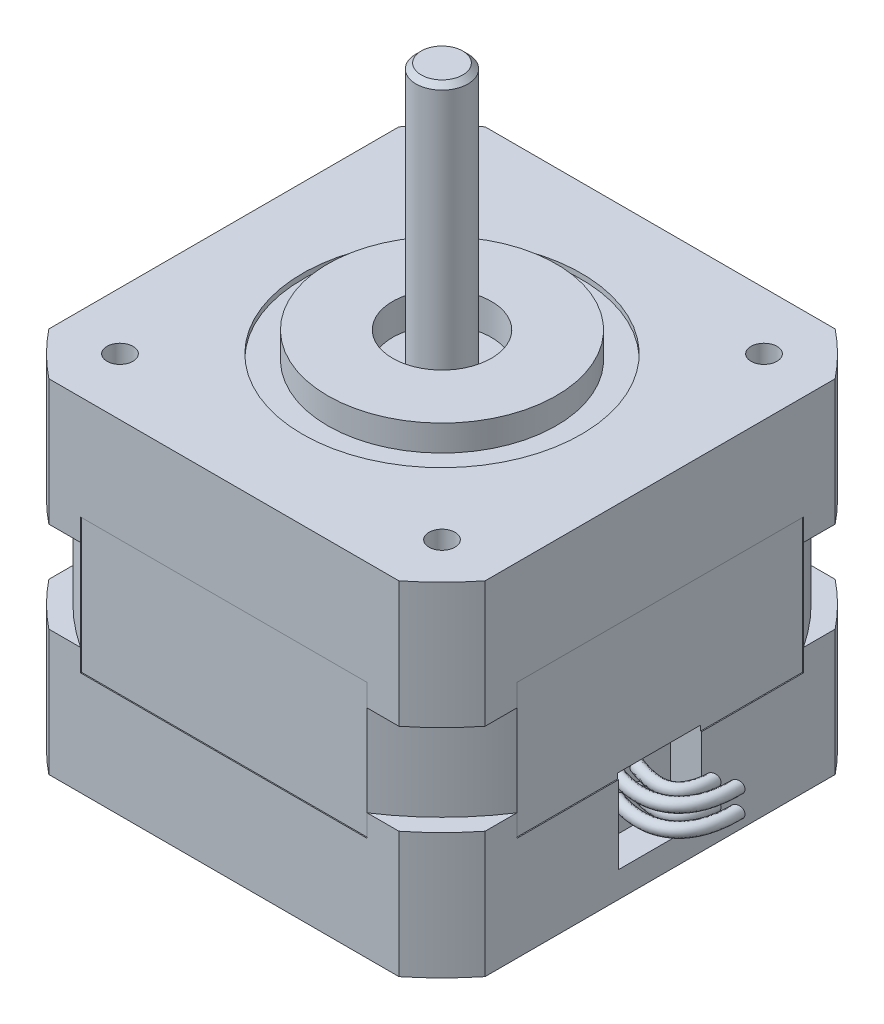
SolidWorks part; units mm, degrees
ref_plane "Front Plane" through (0, 0, 0) normal (0, 0, 1) x (1, 0, 0)
ref_plane "Top Plane" through (0, 0, 0) normal (0, 1, 0) x (1, 0, 0)
ref_plane "Right Plane" through (0, 0, 0) normal (1, 0, 0) x (0, 0, -1)
sketch "Sketch1" plane through (0, 0, 0) normal (0, 1, 0) x (1, 0, 0)
  line L0 (0, -21) -> (0, 21) construction
  line L1 (-21, 16.851) -> (-21, -16.851)
  line L2 (-16.851, -21) -> (16.851, -21)
  line L3 (21, -16.851) -> (21, 16.851)
  line L4 (16.851, 21) -> (-16.851, 21)
  line L5 (-21, 0) -> (21, 0) construction
  arc A0 (-21, 16.851) -> (-16.851, 21) centre (0, 0) cw
  arc A1 (16.851, 21) -> (21, 16.851) centre (0, 0) cw
  arc A2 (21, -16.851) -> (16.851, -21) centre (0, 0) cw
  arc A3 (-21, -16.851) -> (-16.851, -21) centre (0, 0) ccw
  dimension "D3" = 26.925
  dimension "D1" = 42
  dimension "D2" = 42
extrude "Boss-Extrude2" add sketch "Sketch1" along normal blind 33
sketch "Sketch3" plane through (0, 0, 0) normal (0, 0, 1) x (1, 0, 0)
  line L0 (0, -2.0131) -> (0, 34.8611) construction
  line L1 (-30.125, 20.875) -> (-25.125, 20.875)
  line L2 (-30.125, 20.875) -> (-30.125, 12.125)
  line L3 (-30.125, 12.125) -> (-25.125, 12.125)
  line L4 (-25.125, 20.875) -> (-25.125, 12.125)
  line L5 (21, 16.5) -> (-21, 16.5) construction
  line L6 (21, 33) -> (21, 0) construction
  line L7 (-21, 33) -> (-21, 0) construction
  point P13 (-25.125, 16.5)
  dimension "D1" = 8.75
  dimension "D2" = 25.125
  dimension "D3" = 5
revolve "Cut-Revolve1" cut sketch "Sketch3" angle 360 about L0
sketch "Sketch4" plane through (0, 33, 0) normal (0, 1, 0) x (1, 0, 0)
  circle A0 centre (0, 0) radius 13.425
  dimension "D1" = 26.85
extrude "Cut-Extrude1" cut sketch "Sketch4" against normal blind 0.5
sketch "Sketch5" plane through (0, 32.5, 0) normal (0, 1, 0) x (1, 0, 0)
  circle A0 centre (0, 0) radius 11
  dimension "D1" = 22
extrude "Boss-Extrude3" add sketch "Sketch5" along normal blind 2.5
sketch "Sketch6" plane through (0, 35, 0) normal (0, 1, 0) x (1, 0, 0)
  circle A0 centre (0, 0) radius 4.75
  dimension "D1" = 9.5
extrude "Cut-Extrude2" cut sketch "Sketch6" against normal blind 3
sketch "Sketch7" plane through (0, 32, 0) normal (0, 1, 0) x (1, 0, 0)
  circle A0 centre (0, 0) radius 2.5
  dimension "D1" = 5
extrude "Boss-Extrude4" add sketch "Sketch7" along normal blind 25.25
chamfer "Chamfer1" distance 0.5 angle 45 1 edges at (0, 57.25, 2.5)
sketch "Sketch8" plane through (0, 0, 0) normal (0, -1, 0) x (1, 0, 0)
  circle A0 centre (0, 0) radius 4.5
  dimension "D1" = 9
extrude "Cut-Extrude3" cut sketch "Sketch8" against normal blind 3
sketch "Sketch9" plane through (0, 33, 0) normal (0, 1, 0) x (1, 0, 0)
  line L0 (-15.5, 15.5) -> (15.5, 15.5) construction
  line L1 (15.5, 15.5) -> (15.5, -15.5) construction
  line L2 (15.5, -15.5) -> (-15.5, -15.5) construction
  line L3 (-15.5, -15.5) -> (-15.5, 15.5) construction
  point P2 (-15.5, 0)
  point P5 (0, 15.5)
  dimension "D1" = 31
  dimension "D2" = 31
hole_wizard "M3x0.5 Tapped Hole1" positions "Sketch11" profile "Sketch10" tap size "M3x0.5" standard "ANSI Metric"
sketch "Sketch11" plane through (0, 33, 0) normal (0, 1, 0) x (1, 0, 0)
  point P0 (-15.5, -15.5)
  point P3 (-15.5, 15.5)
  point P6 (15.5, 15.5)
  point P9 (15.5, -15.5)
sketch "Sketch10" plane through (-15.5, 33, 15.5) normal (1, 0, 0) x (0, 0, 1)
  line L0 (0, 0) -> (0, 5.2511)
  line L1 (0, 5.2511) -> (1.25, 4.5)
  line L2 (1.25, 4.5) -> (1.25, 0)
  line L5 (1.25, 0) -> (0, 0)
  line L10 (0, 5.2511) -> (-1.25, 4.5) construction
  line L11 (0, -6.35) -> (0, 107.95) construction
  dimension "Tap Drill Dia." = 2.5
  dimension "Tap Drill Depth" = 4.5
  dimension "Drill Angle" = 118
sketch "Sketch12" plane through (21, 0, 0) normal (1, 0, 0) x (0, 0, -1)
  line L0 (-16.851, 0) -> (16.851, 0) construction
  line L1 (-4, 10.5) -> (4, 10.5)
  line L2 (-4, 10.5) -> (-4, 2.5)
  line L3 (-4, 2.5) -> (4, 2.5)
  line L4 (4, 10.5) -> (4, 2.5)
  point P4 (0, 2.5)
  dimension "D1" = 8
  dimension "D2" = 8
  dimension "D3" = 2.5
extrude "Cut-Extrude4" cut sketch "Sketch12" against normal blind 3
sketch "Sketch13" plane through (18, 0, 0) normal (1, 0, 0) x (0, 0, -1)
  circle A0 centre (-1.1125, 7.415) radius 0.6
  circle A1 centre (0.707, 7.415) radius 0.6
  circle A2 centre (-1.1125, 5.3322) radius 0.6
  circle A3 centre (0.707, 5.3322) radius 0.6
  dimension "D1" = 1.2
sketch "Sketch14" plane through (0, 0, 0) normal (0, 1, 0) x (1, 0, 0)
  spline S0 degree 2 poles (17.6767, 0) (23.6461, -2.3668) (23.7984, 3.3576) knots 0 0 0 1 1 1
sweep "Sweep2" add profiles "Sketch13" path "Sketch14"
sketch "Sketch15" plane through (0, 0, -21) normal (0, 0, -1) x (-1, 0, 0)
  line L0 (-13.7937, 12.125) -> (-13.7937, 20.875) construction
  line L1 (-13.7937, 23) -> (13.7937, 23)
  line L2 (-13.7937, 23) -> (-13.7937, 10)
  line L3 (-13.7937, 10) -> (13.7937, 10)
  line L4 (13.7937, 23) -> (13.7937, 10)
  line L5 (13.7937, 20.875) -> (13.7937, 12.125) construction
  point P8 (-13.7937, 16.5)
  point P9 (-13.7937, 16.5)
  dimension "D1" = 13
extrude "Cut-Extrude5" cut sketch "Sketch15" against normal blind 0.1
ref_axis "Axis1" through (0, 0, 0) along (0, 1, 0)
pattern_circular "CirPattern1" count 4 over 360 about axis through (0, 0, 0) along (0, 1, 0) of "Cut-Extrude5"
